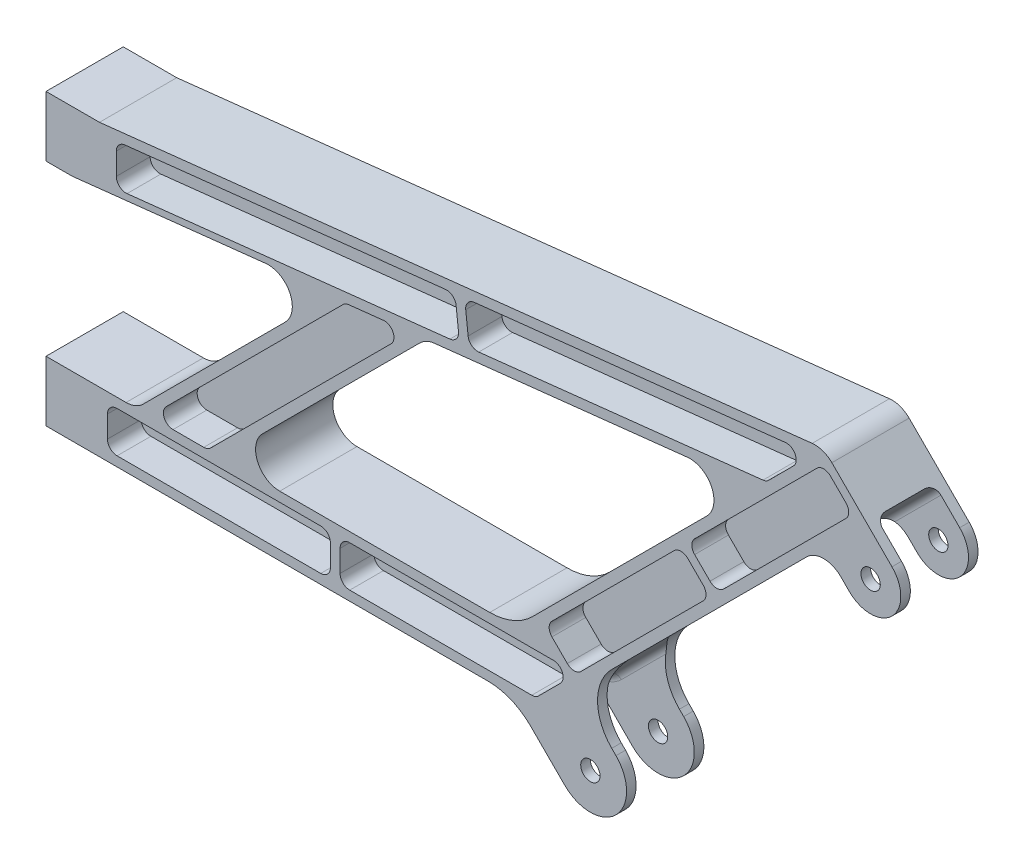
SolidWorks part; units mm, degrees
material "6061-T6 (SS)"
ref_plane "Front Plane" through (0, 0, 0) normal (0, 0, 1) x (1, 0, 0)
ref_plane "Top Plane" through (0, 0, 0) normal (0, 1, 0) x (1, 0, 0)
ref_plane "Right Plane" through (0, 0, 0) normal (1, 0, 0) x (0, 0, -1)
sketch "Sketch1" plane through (0, 0, 0) normal (0, 0, 1) x (1, 0, 0)
  line L1 (-157.7639, -90.8401) -> (-244.7728, -90.8401)
  line L2 (-67.8181, -11.2496) -> (-140.0863, -83.5177)
  line L3 (-16.0497, 33.7315) -> (8.8396, 8.8381)
  line L4 (-12.3744, -5.3033) -> (-8.8388, -8.8388)
  line L5 (-26.5165, -5.3033) -> (-107.2487, -86.0355)
  line L6 (-140.8326, -123.1624) -> (-126.6942, -137.3008)
  line L7 (-158.5102, -115.8401) -> (-341.1373, -115.8401)
  line L8 (-341.1373, -115.8401) -> (-341.1373, -90.8401)
  line L9 (-308.4124, -90.8401) -> (-341.1373, -90.8401)
  line L11 (-341.5776, -20.8403) -> (-331.2717, -20.8403)
  line L12 (-341.5776, -20.8403) -> (-341.5776, 4.1597)
  line L13 (-341.5776, 4.1597) -> (-319.4176, 4.1597)
  line L14 (-107.2487, -114.3198) -> (-105.481, -116.0876)
  line L15 (-319.4176, 4.1597) -> (-24.2138, 36.6012)
  line L17 (-301.3413, -87.9111) -> (-242.4814, -29.0512)
  line L18 (-75.9816, 5.7616) -> (-180.7131, -5.7479)
  line L19 (-251.8438, -73.769) -> (-186.6918, -8.6169)
  line L20 (-250.6448, -12.04) -> (-330.1793, -20.7804)
  arc A4 (8.8388, -8.8388) -> (8.8396, 8.8381) centre (0, 0) ccw
  arc A5 (-8.8388, -8.8388) -> (8.8388, -8.8388) centre (0, 0) ccw
  arc A6 (-12.3744, -5.3033) -> (-26.5165, -5.3033) centre (-19.4454, -12.3744) ccw
  arc A7 (-107.2487, -86.0355) -> (-107.2487, -114.3198) centre (-93.1066, -100.1777) ccw
  arc A8 (-105.481, -137.3008) -> (-105.481, -116.0876) centre (-116.0876, -126.6942) ccw
  arc A9 (-126.6942, -137.3008) -> (-105.481, -137.3008) centre (-116.0876, -126.6942) ccw
  circle A12 centre (-116.0876, -126.6942) radius 4
  circle A13 centre (0, 0) radius 4
  arc A15 (-158.5102, -115.8401) -> (-140.8326, -123.1624) centre (-158.5102, -140.8401) cw
  arc A16 (-157.7639, -90.8401) -> (-140.0863, -83.5177) centre (-157.7639, -65.8401) ccw
  arc A20 (-67.8181, -11.2496) -> (-75.9816, 5.7616) centre (-74.8892, -4.1785) ccw
  arc A21 (-16.0497, 33.7315) -> (-24.2138, 36.6012) centre (-23.1214, 26.661) ccw
  arc A22 (-186.6918, -8.6169) -> (-180.7131, -5.7479) centre (-179.6207, -15.688) cw
  arc A23 (-244.7728, -90.8401) -> (-251.8438, -73.769) centre (-244.7728, -80.8401) cw
  arc A24 (-330.1793, -20.7804) -> (-331.2717, -20.8403) centre (-331.2717, -10.8403) cw
  arc A25 (-308.4124, -90.8401) -> (-301.3413, -87.9111) centre (-308.4124, -80.8401) ccw
  arc A26 (-250.6448, -12.04) -> (-242.4814, -29.0512) centre (-249.5525, -21.9802) cw
  dimension "D2" = 25
  dimension "D3" = 25
  dimension "D7" = 10
  dimension "D6" = 25
  dimension "D1" = 25
  dimension "D4" = 25
  dimension "D5" = 25
  dimension "D8" = 119.9998
extrude "Boss-Extrude1" add sketch "Sketch1" along normal blind 32
sketch "Sketch2" plane through (0, 0, 32) normal (0, 0, 1) x (1, 0, 0)
  line L0 (-107.2487, -86.0355) -> (-26.5165, -5.3033) construction
  line L1 (-137.5386, -110.6685) -> (-128.5386, -101.6685)
  line L2 (-131.367, -94.8401) -> (-215.77, -94.8401)
  line L3 (-67.8181, -11.2496) -> (-140.0863, -83.5177) construction
  line L4 (-107.2487, -86.0355) -> (-26.5165, -5.3033)
  line L5 (-67.8181, -11.2496) -> (-140.0863, -83.5177)
  line L6 (-22.272, 28.6397) -> (-72.893, -21.9813)
  line L7 (-119.9767, -93.1066) -> (-69.3575, -42.4874)
  line L8 (-131.9975, -86.7426) -> (-125.6335, -93.1066)
  line L9 (-10.2515, 22.275) -> (-16.6149, 28.6394)
  line L10 (-64.9897, -14.078) -> (-137.2579, -86.3462) construction
  line L11 (-110.0772, -83.2071) -> (-29.3449, -2.4749) construction
  line L12 (-341.1373, -115.8401) -> (-158.5102, -115.8401) construction
  line L13 (-341.1373, -115.8401) -> (-158.5102, -115.8401)
  line L14 (-312.1373, -111.8401) -> (-227.77, -111.8401)
  line L15 (-341.1373, -111.8401) -> (-158.5102, -111.8401) construction
  line L16 (-341.1373, -90.8401) -> (-341.1373, -115.8401) construction
  line L17 (-316.1373, -98.8401) -> (-316.1373, -107.8401)
  line L18 (-157.7639, -90.8401) -> (-244.7728, -90.8401) construction
  line L19 (8.8396, 8.8381) -> (-16.0497, 33.7315) construction
  line L20 (-140.8326, -123.1624) -> (-126.6942, -137.3008) construction
  line L21 (-65.1149, -38.2448) -> (-77.1357, -26.224) construction
  line L22 (-72.893, -27.6382) -> (-66.5291, -34.0022)
  line L23 (-75.7215, -30.4666) -> (-69.3575, -36.8306)
  line L24 (-81.3783, -30.4666) -> (-131.9975, -81.0858)
  line L25 (-60.8722, -34.0022) -> (-10.2517, 16.6183)
  line L26 (-221.77, -94.8401) -> (-221.77, -111.8401) construction
  line L27 (-219.77, -98.8401) -> (-219.77, -107.8401)
  line L28 (-223.77, -98.8401) -> (-223.77, -107.8401)
  line L29 (-215.77, -111.8401) -> (-140.367, -111.8401)
  line L30 (-227.77, -94.8401) -> (-312.1373, -94.8401)
  line L38 (-308.8907, 1.2925) -> (-176.1091, 15.8845)
  line L39 (-24.2138, 36.6012) -> (-319.4176, 4.1597) construction
  line L40 (-308.0168, -15.7138) -> (-174.2521, -1.0137)
  line L41 (-75.9816, 5.7616) -> (-180.7131, -5.7479) construction
  line L42 (-312.4538, -2.6836) -> (-312.4538, -11.7378)
  line L43 (-32.0118, 24.5568) -> (-42.1838, 14.3847)
  line L44 (-170.145, 16.5399) -> (-168.288, -0.3583) construction
  line L45 (-171.6961, 12.3454) -> (-170.713, 3.3993)
  line L46 (-167.7201, 12.7824) -> (-166.7369, 3.8362)
  line L47 (-164.181, 17.1954) -> (-35.2771, 31.3613)
  line L48 (-162.3239, 0.2971) -> (-44.5753, 13.2371)
  line L49 (-218.5658, -10.7925) -> (-291.7849, -84.0116)
  line L50 (-242.4814, -29.0512) -> (-301.3413, -87.9111) construction
  line L51 (-198.6096, -14.8779) -> (-273.4002, -89.6685)
  line L52 (-186.6918, -8.6169) -> (-251.8438, -73.769) construction
  line L53 (-216.1743, -9.6449) -> (-201.875, -8.0734)
  line L54 (-288.9565, -90.8401) -> (-276.2286, -90.8401)
  line L55 (-341.5776, 4.1597) -> (-341.5776, -20.8403) construction
  arc A0 (-22.272, 28.6397) -> (-16.6149, 28.6394) centre (-19.4436, 25.8113) cw
  arc A1 (-10.2517, 16.6183) -> (-10.2515, 22.275) centre (-13.0801, 19.4468) ccw
  arc A2 (-119.9767, -93.1066) -> (-125.6335, -93.1066) centre (-122.8051, -90.2782) cw
  arc A3 (-131.9975, -81.0858) -> (-131.9975, -86.7426) centre (-129.169, -83.9142) ccw
  arc A4 (-312.1373, -111.8401) -> (-316.1373, -107.8401) centre (-312.1373, -107.8401) cw
  arc A5 (-312.1373, -94.8401) -> (-316.1373, -98.8401) centre (-312.1373, -98.8401) ccw
  arc A6 (-140.367, -111.8401) -> (-137.5386, -110.6685) centre (-140.367, -107.8401) ccw
  arc A7 (-128.5386, -101.6685) -> (-131.367, -94.8401) centre (-131.367, -98.8401) ccw
  arc A8 (-75.7215, -30.4666) -> (-81.3783, -30.4666) centre (-78.5499, -33.295) ccw
  arc A9 (-69.3575, -36.8306) -> (-69.3575, -42.4874) centre (-72.1859, -39.659) cw
  arc A10 (-66.5291, -34.0022) -> (-60.8722, -34.0022) centre (-63.7006, -31.1737) ccw
  arc A11 (-72.893, -27.6382) -> (-72.893, -21.9813) centre (-70.0646, -24.8098) cw
  arc A12 (-223.77, -107.8401) -> (-227.77, -111.8401) centre (-227.77, -107.8401) cw
  arc A13 (-219.77, -107.8401) -> (-215.77, -111.8401) centre (-215.77, -107.8401) ccw
  arc A14 (-219.77, -98.8401) -> (-215.77, -94.8401) centre (-215.77, -98.8401) cw
  arc A15 (-223.77, -98.8401) -> (-227.77, -94.8401) centre (-227.77, -98.8401) ccw
  arc A20 (-44.5753, 13.2371) -> (-42.1838, 14.3847) centre (-45.0122, 17.2132) ccw
  arc A21 (-35.2771, 31.3613) -> (-32.0118, 24.5568) centre (-34.8402, 27.3852) cw
  arc A22 (-166.7369, 3.8362) -> (-162.3239, 0.2971) centre (-162.7609, 4.2732) ccw
  arc A23 (-167.7201, 12.7824) -> (-164.181, 17.1954) centre (-163.744, 13.2193) cw
  arc A24 (-170.713, 3.3993) -> (-174.2521, -1.0137) centre (-174.6891, 2.9623) cw
  arc A25 (-171.6961, 12.3454) -> (-176.1091, 15.8845) centre (-175.6722, 11.9085) ccw
  arc A26 (-308.0168, -15.7138) -> (-312.4538, -11.7378) centre (-308.4538, -11.7378) cw
  arc A27 (-308.8907, 1.2925) -> (-312.4538, -2.6836) centre (-308.4538, -2.6836) ccw
  arc A28 (-198.6096, -14.8779) -> (-201.875, -8.0734) centre (-201.438, -12.0495) ccw
  arc A29 (-218.5658, -10.7925) -> (-216.1743, -9.6449) centre (-215.7374, -13.6209) cw
  arc A30 (-273.4002, -89.6685) -> (-276.2286, -90.8401) centre (-276.2286, -86.8401) cw
  arc A31 (-288.9565, -90.8401) -> (-291.7849, -84.0116) centre (-288.9565, -86.8401) cw
  point P34 (-316.1373, -111.8401)
  point P53 (-78.5499, -27.6382)
  point P58 (-63.7006, -36.8306)
  point P69 (-223.77, -111.8401)
  point P72 (-219.77, -111.8401)
  point P75 (-219.77, -94.8401)
  point P78 (-223.77, -94.8401)
  point P117 (-166.3, -0.1398)
  point P120 (-168.157, 16.7584)
  point P123 (-170.276, -0.5768)
  point P126 (-172.1331, 16.3215)
  dimension "D2" = 4
  dimension "D6" = 4
  dimension "D11" = 4
  dimension "D13" = 4
  dimension "D16" = 4
  dimension "D22" = 4
  dimension "D19" = 4
  dimension "D4" = 25
  dimension "D5" = 4
  dimension "D7" = 4
  dimension "D8" = 4
  dimension "D9" = 32
  dimension "D10" = 2
  dimension "D12" = 2
  dimension "D14" = 4
  dimension "D15" = 4
  dimension "D17" = 4
  dimension "D18" = 4
  dimension "D20" = 4
  dimension "D21" = 2
  dimension "D23" = 4
  dimension "D1" = 4
  dimension "D3" = 4
extrude "Cut-Extrude1" cut sketch "Sketch2" against normal blind 14 contours L38 A27 L42 A26 L40 A24 L45 A25 | A23 L46 A22 L48 A20 L43 A21 L47 | A31 L54 A30 L51 A28 L53 A29 L49 | A11 L22 A10 L25 A1 L9 A0 L6 | A9 L23 A8 L24 A3 L8 A2 L7 | A14 L27 A13 L29 A6 L1 A7 L2 | L28 A15 L30 A5 L17 A4 L14 A12 region at (-175.3079, -103.1533, 32) region at (-41.5723, -2.6814, 32) region at (-100.6775, -61.7866, 32) region at (-269.9537, -103.3401, 32) region at (-241.8227, 0.0982, 32) region at (-100.9045, 15.7508, 32) region at (-245.4094, -49.7028, 32)
ref_plane "Plane1" through (0, 0, 16) normal (0, 0, 1) x (1, 0, 0)
mirror "Mirror1" about plane through (0, 0, 16) normal (0, 0, 1) of "Cut-Extrude1"
sketch "Sketch3" plane through (0, 0, 16) normal (0, 0, 1) x (1, 0, 0)
  line L0 (-158.5102, -115.8401) -> (-141.1954, -115.8401)
  line L1 (-98.969, -77.7558) -> (-134.1243, -112.9111)
  line L2 (-107.2487, -86.0355) -> (-26.5165, -5.3033) construction
  line L3 (-158.5102, -115.8401) -> (-116.5971, -149.2186)
  line L4 (-116.5971, -149.2186) -> (-66.3597, -110.0186)
  line L5 (-66.3597, -110.0186) -> (-98.969, -77.7558)
  line L6 (-29.0156, -7.8024) -> (7.8698, 29.083)
  line L7 (7.8698, 29.083) -> (26.3533, -15.3879)
  line L8 (26.3533, -15.3879) -> (-12.041, -17.819)
  line L9 (-12.041, -17.819) -> (-29.0156, -7.8024)
  arc A0 (-134.1243, -112.9111) -> (-141.1954, -115.8401) centre (-141.1954, -105.8401) cw
  dimension "D1" = 10
extrude "Cut-Extrude2" cut sketch "Sketch3" against normal blind 12.0515 and the other way blind 12.0515
sketch "Sketch5" plane through (0, 0, 16) normal (0, 0, 1) x (1, 0, 0)
  line L0 (0, -24.7236) -> (0, -90.9031)
fillet "Fillet1" radius 4 2 edges at (-14.1417, 7.0715, 28.0515) (-14.1417, 7.0715, 3.9485)
fillet "Fillet2" radius 4 6 edges at (-149.8528, -115.8401, 3.9485) (-137.3686, -115.0789, 3.9485) (-149.8528, -115.8401, 28.0515) (-137.3686, -115.0789, 28.0515) (-120.6865, -99.4733, 3.9485) (-120.6865, -99.4733, 28.0515)
sketch "Sketch6" plane through (-341.1373, 0, 0) normal (-1, 0, 0) x (0, 0, 1)
  line L4 (0, -90.8401) -> (0, -115.8401)
  line L5 (0, -115.8401) -> (32, -115.8401)
  line L6 (32, -115.8401) -> (32, -90.8401)
  line L7 (32, -90.8401) -> (0, -90.8401)
  line L8 (0, -90.8401) -> (0, -115.8401)
  line L9 (0, -115.8401) -> (32, -115.8401)
  line L10 (32, -115.8401) -> (32, -90.8401)
  line L11 (32, -90.8401) -> (0, -90.8401)
  dimension "D1" = 0
extrude "Boss-Extrude2" add sketch "Sketch6" along normal up to surface (0.4403 mm away)
sketch "Sketch7" plane through (-341.5776, 0, 0) normal (-1, 0, 0) x (0, 0, 1)
  line L0 (32, -115.8401) -> (32, -90.8401) construction
  line L1 (32, -90.8401) -> (0, -90.8401) construction
  line L2 (0, -90.8401) -> (0, -115.8401) construction
  line L3 (0, -115.8401) -> (32, -115.8401) construction
  line L4 (0, 4.1597) -> (0, -20.8403) construction
  line L5 (0, -20.8403) -> (32, -20.8403) construction
  line L6 (32, -20.8403) -> (32, 4.1597) construction
  line L7 (32, 4.1597) -> (0, 4.1597) construction
  line L8 (32, -115.8401) -> (32, -90.8401)
  line L9 (32, -90.8401) -> (0, -90.8401)
  line L10 (0, -90.8401) -> (0, -115.8401)
  line L11 (0, -115.8401) -> (32, -115.8401)
  line L12 (0, 4.1597) -> (0, -20.8403)
  line L13 (0, -20.8403) -> (32, -20.8403)
  line L14 (32, -20.8403) -> (32, 4.1597)
  line L15 (32, 4.1597) -> (0, 4.1597)
  line L16 (0, -115.8401) -> (32, -90.8401)
  line L17 (32, 4.1597) -> (0, -20.8403)
  circle A0 centre (16, -103.3401) radius 4
  circle A1 centre (16, -8.3403) radius 4
  dimension "D1" = 8
  dimension "D2" = 8
extrude "Cut-Extrude3" cut sketch "Sketch7" against normal blind 14 contours L17 A1 | L17 A1 | L16 A0 | L16 A0 region at (-341.5776, -104.6779, 17.0451) region at (-341.5776, -102.0023, 14.9549) region at (-341.5776, -7.0025, 14.9549) region at (-341.5776, -9.6781, 17.0451)
